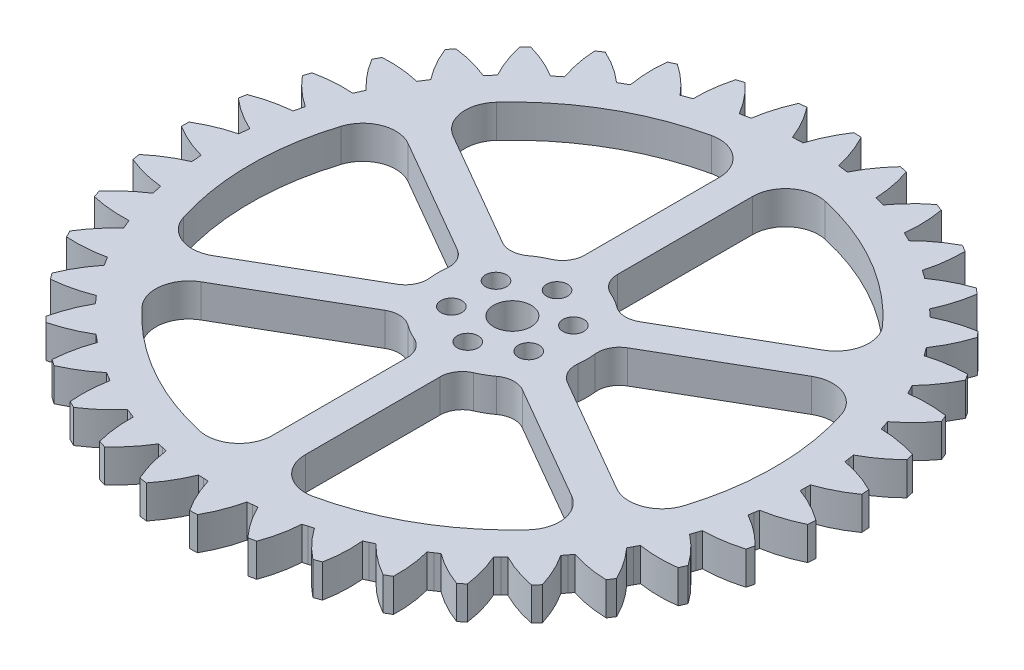
SolidWorks part; units mm, degrees
ref_plane "Front Plane" through (0, 0, 0) normal (0, 0, 1) x (1, 0, 0)
ref_plane "Top Plane" through (0, 0, 0) normal (0, 1, 0) x (1, 0, 0)
ref_plane "Right Plane" through (0, 0, 0) normal (1, 0, 0) x (0, 0, -1)
sketch "Sketch1" plane through (0, 0, 0) normal (0, 1, 0) x (1, 0, 0)
  line L6 (-5, -2.8868) -> (0, -5.7735)
  line L7 (0, -5.7735) -> (5, -2.8868)
  line L8 (5, -2.8868) -> (5, 2.8868)
  line L9 (5, 2.8868) -> (0, 5.7735)
  line L10 (0, 5.7735) -> (-5, 2.8868)
  line L11 (-5, 2.8868) -> (-5, -2.8868)
  line L12 (-5, -2.8868) -> (0, -5.7735)
  line L13 (0, -5.7735) -> (5, -2.8868)
  line L14 (5, -2.8868) -> (5, 2.8868)
  line L15 (5, 2.8868) -> (0, 5.7735)
  line L16 (0, 5.7735) -> (-5, 2.8868)
  line L17 (-5, 2.8868) -> (-5, -2.8868)
  circle A0 centre (0, 0) radius 28.4436 construction
  circle A1 centre (0, 0) radius 28.4436
  circle A3 centre (-3.5074, 2.025) radius 0.95
  circle A4 centre (-3.5074, 2.025) radius 0.95
  circle A5 centre (0, 0) radius 1.7
  circle A6 centre (0, 0) radius 1.7
  circle A7 centre (-3.5074, -2.025) radius 0.95
  circle A8 centre (-3.5074, -2.025) radius 0.95
  circle A9 centre (0, -4.05) radius 0.95
  circle A10 centre (0, -4.05) radius 0.95
  circle A11 centre (3.5074, -2.025) radius 0.95
  circle A12 centre (3.5074, -2.025) radius 0.95
  circle A13 centre (3.5074, 2.025) radius 0.95
  circle A14 centre (3.5074, 2.025) radius 0.95
  circle A15 centre (0, 4.05) radius 0.95
  circle A16 centre (0, 4.05) radius 0.95
  dimension "D1" = 0
  dimension "D2" = 0
  dimension "D3" = 0
  dimension "D4" = 0
  dimension "D5" = 0
  dimension "D6" = 0
  dimension "D7" = 0
  dimension "D8" = 0
sketch "Sketch2"
sketch "Sketch5" plane through (0, 0, 0) normal (0, 1, 0) x (1, 0, 0)
  line L0 (0, 0) -> (29.8198, 2.1775) construction
  line L1 (29.8449, 1.834) -> (29.7947, 2.5211) construction
  line L2 (29.7947, 2.5211) -> (29.8198, 2.1775)
  line L3 (0, 0) -> (26.45, 4.0908)
  line L4 (26.45, 4.0908) -> (26.5209, 3.6382)
  line L5 (26.4813, 3.8882) -> (26.4186, 4.2934) construction
  line L6 (29.8449, 1.834) -> (29.8198, 2.1775)
  line L7 (26.7636, -0.205) -> (26.7681, 0.253)
  line L8 (0, 0) -> (26.7636, -0.205)
  arc A0 (26.5209, 3.6382) -> (29.7947, 2.5211) centre (24.2901, -8.2545) cw
  arc A1 (26.7681, 0.253) -> (29.8449, 1.834) centre (22.8333, 11.6956) ccw
  dimension "D1" = 4.615
extrude "Boss-Extrude1" add sketch "Sketch5" along normal blind 1.5 and the other way blind 1.5
pattern_circular "CirPattern2" count 39 over 360 about axis through (0, -1.5, 0) along (0, 1, 0) of "Boss-Extrude1"
sketch "Sketch3" plane through (0, 1.5, 0) normal (0, 1, 0) x (1, 0, 0)
  circle A0 centre (-3.5074, 2.025) radius 0.95 construction
  circle A1 centre (-3.5074, -2.025) radius 0.95 construction
  circle A2 centre (0, -4.05) radius 0.95 construction
  circle A3 centre (3.5074, -2.025) radius 0.95 construction
  circle A4 centre (3.5074, 2.025) radius 0.95 construction
  circle A5 centre (0, 4.05) radius 0.95 construction
  circle A6 centre (-3.5074, 2.025) radius 0.95
  circle A7 centre (-3.5074, -2.025) radius 0.95
  circle A8 centre (0, -4.05) radius 0.95
  circle A9 centre (3.5074, -2.025) radius 0.95
  circle A10 centre (3.5074, 2.025) radius 0.95
  circle A11 centre (0, 4.05) radius 0.95
  circle A12 centre (0, 0) radius 1.7 construction
  circle A13 centre (0, 0) radius 1.7
extrude "Cut-Extrude1" cut sketch "Sketch3" against normal through all
sketch "Sketch4" plane through (0, 1.5, 0) normal (0, 1, 0) x (1, 0, 0)
  line L0 (0, 0) -> (43301.2702, 25000) construction
  line L1 (-1000, 0) -> (49000, 0) construction
  line L2 (6.4704, 2.0036) -> (21.2896, 10.5595)
  line L3 (6.4704, -2.0036) -> (21.2896, -10.5595)
  line L4 (26.7621, -0.4101) -> (26.7652, 0) construction
  circle A0 centre (0, 0) radius 1.7 construction
  circle A1 centre (0, 0) radius 5.7735 construction
  circle A2 centre (0, 0) radius 26.7644 construction
  circle A4 centre (0, 0) radius 6.7735 construction
  arc A5 (6.4704, 2.0036) -> (6.4704, -2.0036) centre (0, 0) cw
  arc A6 (21.2896, 10.5595) -> (21.2896, -10.5595) centre (0, 0) cw
  circle A7 centre (0, 0) radius 23.7644 construction
  dimension "D3" = 1.5
  dimension "D1" = 3
  dimension "D2" = 1
extrude "Cut-Extrude2" cut sketch "Sketch4" against normal through all
fillet "Fillet1" radius 3 2 edges at (21.2896, 0, 10.5595) (21.2896, 0, -10.5595)
fillet "Fillet2" radius 2 2 edges at (6.4704, 0, 2.0036) (6.4704, 0, -2.0036)
pattern_circular "CirPattern1" count 6 over 360 about axis through (0, -1.5, 0) along (0, 1, 0) of "Cut-Extrude2", "Fillet1", "Fillet2" reverse direction yes
